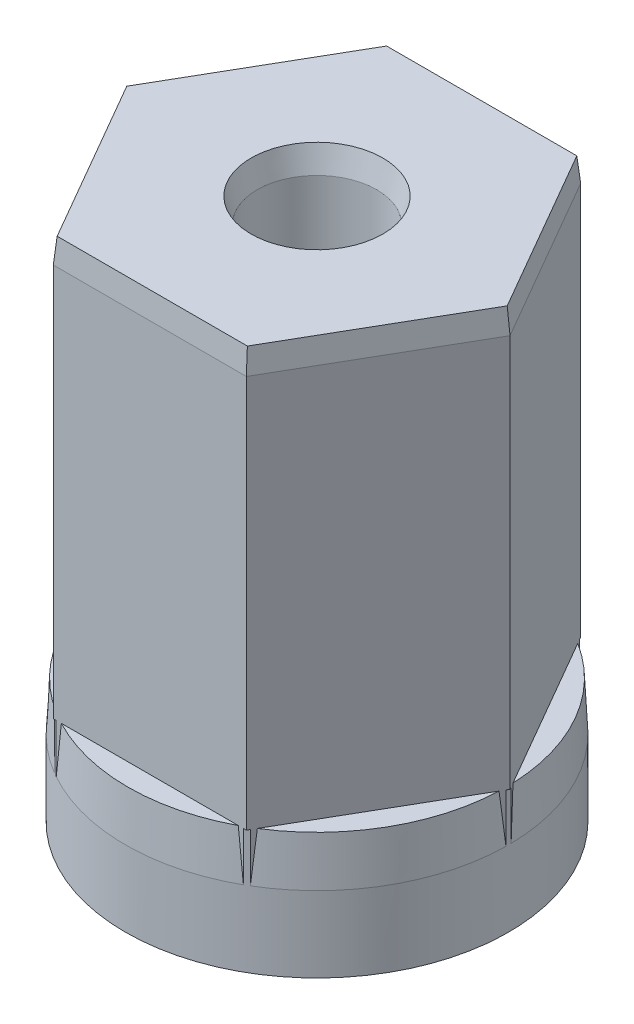
SolidWorks part; units mm, degrees
ref_plane "Front Plane" through (0, 0, 0) normal (0, 0, 1) x (1, 0, 0)
ref_plane "Top Plane" through (0, 0, 0) normal (0, 1, 0) x (1, 0, 0)
ref_plane "Right Plane" through (0, 0, 0) normal (1, 0, 0) x (0, 0, -1)
sketch "Sketch1" plane through (0, 0, 0) normal (0, 1, 0) x (1, 0, 0)
  circle A0 centre (0, 0) radius 8 construction
  circle A1 centre (0, 0) radius 7.85
  dimension "D1" = 16
  dimension "D2" = 0.15
extrude "Boss-Extrude1" add sketch "Sketch1" along normal blind 5.1
sketch "Sketch2" plane through (0, 5.1, 0) normal (0, 1, 0) x (1, 0, 0)
  line L0 (3.9548, -6.85) -> (7.9097, 0)
  line L1 (4.0126, 6.95) -> (-4.0126, 6.95) construction
  line L2 (-4.0126, 6.95) -> (-8.0252, 0) construction
  line L3 (-8.0252, 0) -> (-4.0126, -6.95) construction
  line L4 (-4.0126, -6.95) -> (4.0126, -6.95) construction
  line L5 (4.0126, -6.95) -> (8.0252, 0) construction
  line L6 (8.0252, 0) -> (4.0126, 6.95) construction
  line L7 (7.9097, 0) -> (3.9548, 6.85)
  line L8 (3.9548, 6.85) -> (-3.9548, 6.85)
  line L9 (-3.9548, 6.85) -> (-7.9097, 0)
  line L10 (-7.9097, 0) -> (-3.9548, -6.85)
  line L11 (-3.9548, -6.85) -> (3.9548, -6.85)
  circle A0 centre (0, 0) radius 6.95 construction
  dimension "D1" = 13.9
  dimension "D2" = 0.1
extrude "Boss-Extrude2" add sketch "Sketch2" along normal offset from surface (17.1 mm away) 1
chamfer "Chamfer1" distance 2 distance2 0.1 6 edges at (-6.7983, 5.1, -3.925) (0, 5.1, -7.85) (6.7983, 5.1, -3.925) (6.7983, 5.1, 3.925) (0, 5.1, 7.85) (-6.7983, 5.1, 3.925) first distance on face at (0, 5.1, 0)
chamfer "Chamfer2" distance 0.1 distance2 1 6 edges at (-5.9323, 22.2, -3.425) (0, 22.2, -6.85) (5.9323, 22.2, -3.425) (5.9323, 22.2, 3.425) (0, 22.2, 6.85) (-5.9323, 22.2, 3.425) first distance on face at (0, 22.2, 0)
sketch "Sketch3" plane through (0, 22.2, 0) normal (0, 1, 0) x (1, 0, 0)
  line L1 (0, -2.45) -> (3.2079, -2.45) construction
  circle A0 centre (0, 0) radius 2.45
  dimension "D1" = 4.9
extrude "Cut-Extrude1" cut sketch "Sketch3" against normal through all
sketch "Sketch4" plane through (0, 0, 0) normal (0, -1, 0) x (1, 0, 0)
  circle A1 centre (0, 0) radius 2.45 construction
  circle A2 centre (0, 0) radius 3.95
  circle A3 centre (0, 0) radius 3.95
  circle A4 centre (0, 0) radius 2.45
  dimension "D1" = 1.5
extrude "Boss-Extrude3" add sketch "Sketch4" along normal offset from surface (2.3 mm away) 1.5
chamfer "Chamfer4" distance 0.25 distance2 1 1 edges at (0, 22.2, 2.45) first distance on face at (0, 22.2, 2.45)
equation "\"Tolerance\"=0.15"
equation "\"D2@Sketch1\"=\"Tolerance\""
